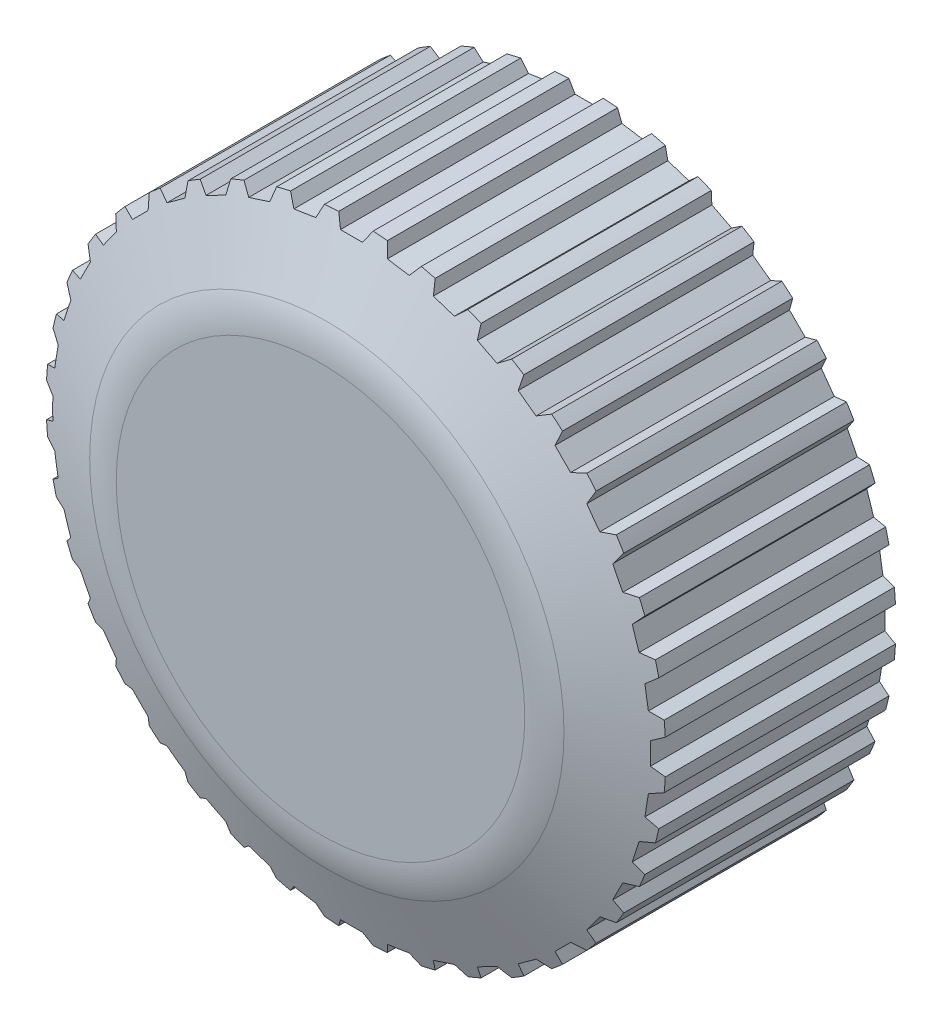
SolidWorks part; units mm, degrees
ref_plane "Plan de face" through (0, 0, 0) normal (0, 0, 1) x (1, 0, 0)
ref_plane "Plan de dessus" through (0, 0, 0) normal (0, 1, 0) x (1, 0, 0)
ref_plane "Plan de droite" through (0, 0, 0) normal (1, 0, 0) x (0, 0, -1)
sketch "Esquisse1" plane through (0, 0, 0) normal (0, 0, 1) x (1, 0, 0)
  circle A0 centre (0, 0) radius 14
  dimension "D1" = 28
extrude "Boss.-Extru.1" add sketch "Esquisse1" along normal blind 12
sketch "Esquisse2" plane through (0, 0, 12) normal (0, 0, 1) x (1, 0, 0)
  line L0 (-1.6547, 15.5) -> (-0.5, 13.5)
  line L1 (-0.5, 13.5) -> (0.5, 13.5)
  line L2 (0.5, 13.5) -> (1.6547, 15.5)
  line L3 (1.6547, 15.5) -> (-1.6547, 15.5)
  line L4 (0, 0) -> (0, 21.1749) construction
  circle A0 centre (0, 0) radius 14 construction
  dimension "D1" = 60
  dimension "D2" = 120
  dimension "D3" = 1
  dimension "D4" = 0.5
  dimension "D5" = 13.5
  dimension "D6" = 2
extrude "Enlèv. mat.-Extru.1" cut sketch "Esquisse2" against normal through all
sketch "Esquisse3" plane through (0, 0, 0) normal (1, 0, 0) x (0, 0, -1)
  line L0 (-18.0975, 0) -> (6.4366, 0) construction
sketch "Esquisse4" plane through (0, 0, 0) normal (0, 0, 1) x (1, 0, 0)
  line L0 (-17.1579, 0) -> (18.8007, 0) construction
pattern_circular "Répétition circulaire1" count 40 over 360 about axis through (0, 0, 12) along (0, 0, -1) of "Enlèv. mat.-Extru.1"
sketch "Esquisse5" plane through (0, 0, 0) normal (0, 1, 0) x (1, 0, 0)
  line L0 (10, -12) -> (14, -10.4)
  line L1 (14, -10.4) -> (14, -12)
  line L2 (14, -12) -> (10, -12)
  line L3 (0, -18.0975) -> (0, 6.4366) construction
  line L4 (-17.1579, 0) -> (18.8007, 0) construction
  dimension "D1" = 14
  dimension "D2" = 12
  dimension "D3" = 4
  dimension "D4" = 1.6
revolve "Enlèvement de matière-Révolution1" cut sketch "Esquisse5" angle 360 about L0
fillet "Congé1" radius 4 1 edges at (10, 0, 12)
sketch "Esquisse6" plane through (0, 0, 0) normal (0, 0, -1) x (-1, 0, 0)
  circle A0 centre (0, 0) radius 4
  dimension "D1" = 8
extrude "Enlèv. mat.-Extru.2" cut sketch "Esquisse6" against normal blind 6
